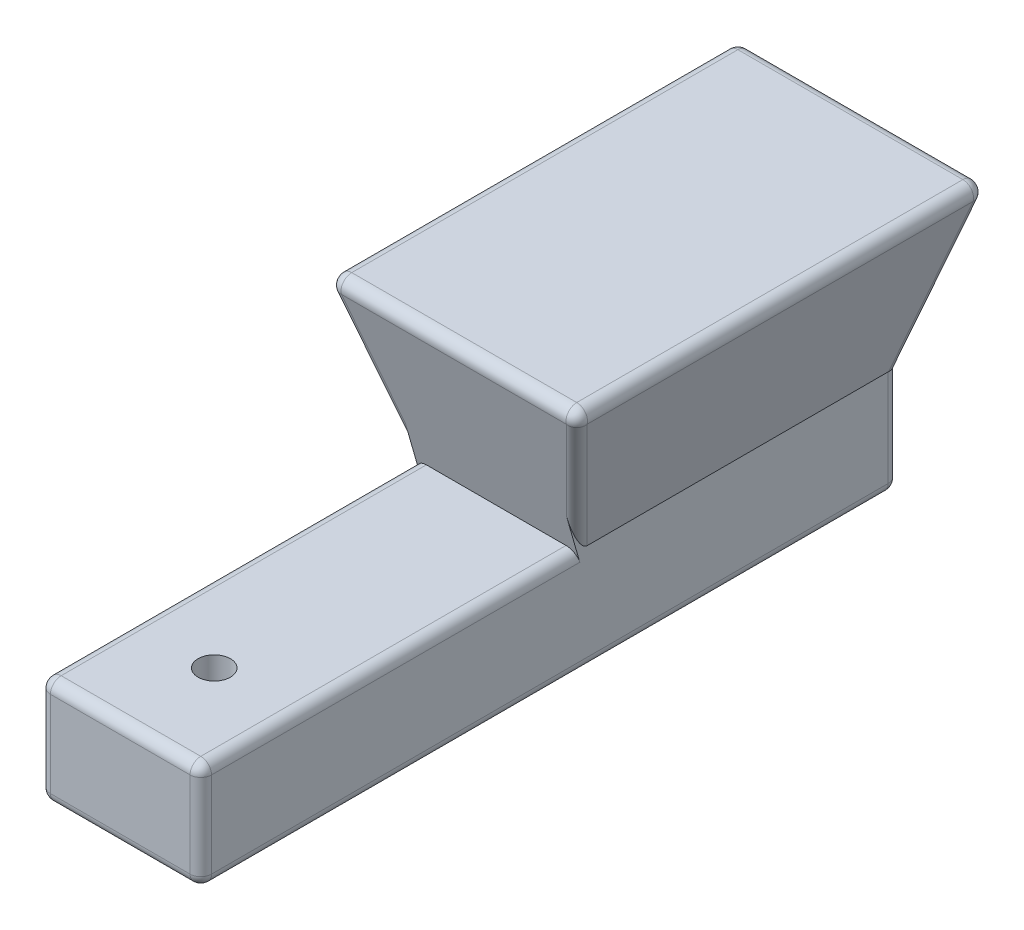
SolidWorks part; units mm, degrees
ref_plane "Front Plane" through (0, 0, 0) normal (0, 0, 1) x (1, 0, 0)
ref_plane "Top Plane" through (0, 0, 0) normal (0, 1, 0) x (1, 0, 0)
ref_plane "Right Plane" through (0, 0, 0) normal (1, 0, 0) x (0, 0, -1)
sketch "Sketch2" plane through (0, 0, 0) normal (0, 1, 0) x (1, 0, 0)
  line L1 (-37.3094, 55.426) -> (-22.3094, 55.426)
  line L2 (-37.3094, 55.426) -> (-37.3094, -9.574)
  line L3 (-37.3094, -9.574) -> (-22.3094, -9.574)
  line L4 (-22.3094, 55.426) -> (-22.3094, -9.574)
  dimension "D1" = 15
  dimension "m" = 65
extrude "Boss-Extrude1" add sketch "Sketch2" along normal blind 10
sketch "Sketch3" plane through (0, 10, 0) normal (0, 1, 0) x (1, 0, 0)
  circle A0 centre (-29.8094, -0.824) radius 1.5
  dimension "D2" = 3
extrude "Cut-Extrude1" cut sketch "Sketch3" against normal through all
sketch "Sketch4" plane through (0, 10, 0) normal (0, 1, 0) x (1, 0, 0)
  line L0 (-22.3094, -9.574) -> (-22.3094, 55.426) construction
  line L1 (-37.3094, 55.426) -> (-22.3094, 55.426)
  line L2 (-37.3094, 55.426) -> (-37.3094, 25.426)
  line L3 (-37.3094, 25.426) -> (-22.3094, 25.426)
  line L4 (-22.3094, 55.426) -> (-22.3094, 25.426)
  dimension "D1" = 30
extrude "Boss-Extrude2" add sketch "Sketch4" along normal blind 15 draft 16 draft outward yes
fillet "Fillet1" radius 1 7 edges at (-29.8094, 25, -59.7272) (-41.6106, 25, -40.426) (-29.8094, 25, -21.1248) (-18.0082, 25, -40.426) (-22.3094, 10, -7.926) (-29.8094, 10, 9.574) (-37.3094, 10, -7.926)
fillet "Fillet2" radius 1 6 edges at (-22.6023, 9.7071, 9.2811) (-22.3094, 0, -22.926) (-29.8094, 0, -55.426) (-37.3094, 5, -55.426) (-22.3094, 5, -55.426) (-22.3094, 4.5, 9.574)
fillet "Fillet3" radius 1 6 edges at (-37.0165, 9.7071, 9.2811) (-22.6023, 0.2929, 9.2811) (-37.0165, 0.2929, -55.1331) (-37.3094, 4.5, 9.574) (-30.3094, 0, 9.574) (-37.3094, 0, -22.426)
fillet "Fillet4" radius 1 8 edges at (-18.5366, 24.6018, -59.1988) (-18.5366, 24.6018, -21.6532) (-41.0822, 24.6018, -21.6532) (-41.0822, 24.6018, -59.1988) (-20.4882, 16.3515, -57.2473) (-20.3417, 16.8622, -23.4583) (-39.2771, 16.8622, -23.4583) (-39.1307, 16.3515, -57.2473)
